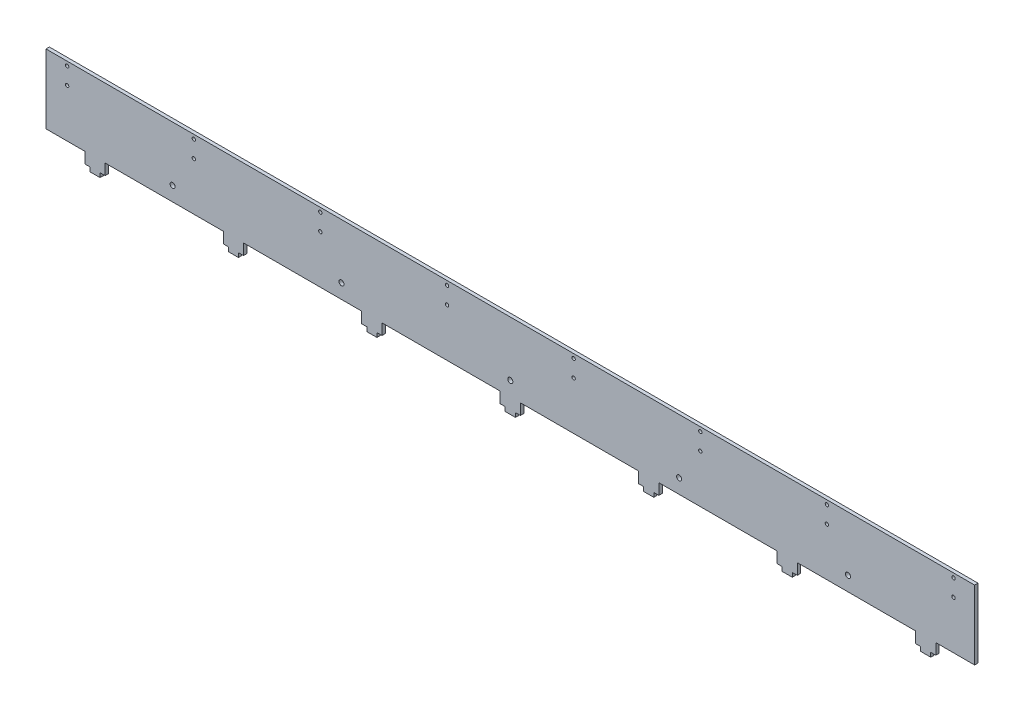
SolidWorks part; units mm, degrees
ref_plane "Спереди" through (0, 0, 0) normal (0, 0, 1) x (1, 0, 0)
ref_plane "Сверху" through (0, 0, 0) normal (0, 1, 0) x (1, 0, 0)
ref_plane "Справа" through (0, 0, 0) normal (1, 0, 0) x (0, 0, -1)
sketch "Эскиз1" plane through (0, 0, 0) normal (0, 0, 1) x (1, 0, 0)
  line L1 (-550, -47.5) -> (550, -47.5)
  line L2 (-550, -47.5) -> (-550, 47.5)
  line L3 (-550, 47.5) -> (550, 47.5)
  line L4 (550, -47.5) -> (550, 47.5)
  line L5 (0, 47.5) -> (0, -47.5) construction
  line L6 (-550, 0) -> (550, 0) construction
  point P0 (0, 0)
  dimension "D1" = 95
  dimension "D2" = 1100
extrude "Бобышка-Вытянуть1" add sketch "Эскиз1" along normal mid plane 4
sketch "Эскиз2" plane through (0, 0, 2) normal (0, 0, 1) x (1, 0, 0)
  line L0 (-550, -47.5) -> (550, -47.5) construction
  line L1 (-550, -47.5) -> (-504, -47.5)
  line L2 (-550, -47.5) -> (-550, -34.5)
  line L3 (-550, -34.5) -> (-504, -34.5)
  line L4 (-504, -47.5) -> (-504, -34.5)
  line L5 (550, -47.5) -> (504, -47.5)
  line L6 (550, -47.5) -> (550, -34.5)
  line L7 (550, -34.5) -> (504, -34.5)
  line L8 (504, -47.5) -> (504, -34.5)
  line L9 (-480, -34.5) -> (-340, -34.5)
  line L10 (-480, -34.5) -> (-480, -47.5)
  line L11 (-480, -47.5) -> (-340, -47.5)
  line L12 (-340, -34.5) -> (-340, -47.5)
  line L14 (-316, -34.5) -> (-176, -34.5)
  line L15 (-316, -34.5) -> (-316, -47.5)
  line L16 (-316, -47.5) -> (-176, -47.5)
  line L17 (-176, -34.5) -> (-176, -47.5)
  line L18 (-152, -34.5) -> (-12, -34.5)
  line L19 (-152, -34.5) -> (-152, -47.5)
  line L20 (-152, -47.5) -> (-12, -47.5)
  line L21 (-12, -34.5) -> (-12, -47.5)
  line L22 (12, -34.5) -> (152, -34.5)
  line L23 (12, -34.5) -> (12, -47.5)
  line L24 (12, -47.5) -> (152, -47.5)
  line L25 (152, -34.5) -> (152, -47.5)
  line L26 (176, -34.5) -> (316, -34.5)
  line L27 (176, -34.5) -> (176, -47.5)
  line L28 (176, -47.5) -> (316, -47.5)
  line L29 (316, -34.5) -> (316, -47.5)
  line L30 (340, -34.5) -> (480, -34.5)
  line L31 (340, -34.5) -> (340, -47.5)
  line L32 (340, -47.5) -> (480, -47.5)
  line L33 (480, -34.5) -> (480, -47.5)
  point P20 (-316, -41)
  point P25 (-152, -41)
  point P26 (152, -41)
  point P39 (340, -41)
  dimension "D1" = 13
  dimension "D5" = 24
  dimension "D6" = 140
  dimension "D7" = 24
  dimension "D2" = 24
  dimension "D3" = 140
  dimension "D4" = 140
  dimension "D8" = 24
  dimension "D9" = 140
  dimension "D10" = 24
  dimension "D11" = 140
  dimension "D12" = 24
  dimension "D13" = 140
  dimension "D14" = 24
extrude "Вырез-Вытянуть1" cut sketch "Эскиз2" against normal through all
sketch "Эскиз3" plane through (0, 0, 2) normal (0, 0, 1) x (1, 0, 0)
  line L0 (550, 47.5) -> (-550, 47.5) construction
  line L1 (-550, 47.5) -> (-550, -34.5) construction
  circle A0 centre (-525, 42.5) radius 2
  circle A1 centre (-525, 22.5) radius 2
  dimension "D1" = 4
  dimension "D2" = 5
  dimension "D3" = 20
  dimension "D4" = 25
extrude "Вырез-Вытянуть2" cut sketch "Эскиз3" against normal through all
pattern_linear "Линейный массив1" count 8 spacing 150 along (1, 0, 0) of "Вырез-Вытянуть2"
sketch "Эскиз4" plane through (0, 0, -2) normal (0, 0, -1) x (-1, 0, 0)
  circle A1 centre (-400, -17.5) radius 3
  circle A2 centre (-400, -17.5) radius 3
  dimension "D1" = 0
extrude "Вырез-Вытянуть3" cut sketch "Эскиз4" against normal through all
pattern_linear "Линейный массив2" count 5 spacing 200 along (-1, 0, 0) of "Вырез-Вытянуть3"
sketch "Эскиз5" plane through (0, -47.5, 0) normal (0, -1, 0) x (1, 0, 0)
  line L0 (492, -2) -> (492, 2) construction
  line L1 (480, 2) -> (504, 2) construction
  line L2 (328, -2) -> (328, 2) construction
  line L3 (316, -2) -> (340, -2) construction
  line L4 (504, 2) -> (480, 2)
  line L5 (480, 2) -> (480, -2)
  line L6 (480, -2) -> (504, -2)
  line L7 (504, -2) -> (504, 2)
  line L8 (498, 2) -> (486, 2)
  line L9 (486, 2) -> (486, -2)
  line L10 (486, -2) -> (498, -2)
  line L11 (498, -2) -> (498, 2)
  line L12 (316, 2) -> (340, 2) construction
  line L13 (164, -2) -> (164, 2) construction
  line L14 (316, -2) -> (340, -2)
  line L15 (340, -2) -> (340, 2)
  line L16 (340, 2) -> (316, 2)
  line L17 (316, 2) -> (316, -2)
  line L18 (322, -2) -> (334, -2)
  line L19 (334, -2) -> (334, 2)
  line L20 (334, 2) -> (322, 2)
  line L21 (322, 2) -> (322, -2)
  line L22 (152, -2) -> (176, -2) construction
  line L23 (152, 2) -> (176, 2) construction
  line L24 (0, -2) -> (0, 2) construction
  line L25 (176, 2) -> (152, 2)
  line L26 (152, 2) -> (152, -2)
  line L27 (152, -2) -> (176, -2)
  line L28 (176, -2) -> (176, 2)
  line L29 (170, 2) -> (158, 2)
  line L30 (158, 2) -> (158, -2)
  line L31 (158, -2) -> (170, -2)
  line L32 (170, -2) -> (170, 2)
  line L33 (-12, -2) -> (12, -2) construction
  line L34 (-12, 2) -> (12, 2) construction
  line L36 (-12, -2) -> (12, -2)
  line L37 (12, -2) -> (12, 2)
  line L38 (12, 2) -> (-12, 2)
  line L39 (-12, 2) -> (-12, -2)
  line L40 (-6, -2) -> (6, -2)
  line L41 (6, -2) -> (6, 2)
  line L42 (6, 2) -> (-6, 2)
  line L43 (-6, 2) -> (-6, -2)
  line L44 (-480, 2) -> (-504, 2) construction
  line L46 (-504, -2) -> (-480, -2) construction
  line L48 (-316, 2) -> (-340, 2) construction
  line L50 (-340, -2) -> (-316, -2) construction
  line L52 (-152, 2) -> (-176, 2) construction
  line L54 (-176, -2) -> (-152, -2) construction
  line L56 (-486, 2) -> (-498, 2)
  line L57 (-498, 2) -> (-498, -2)
  line L58 (-498, -2) -> (-486, -2)
  line L59 (-486, -2) -> (-486, 2)
  line L60 (-322, 2) -> (-334, 2)
  line L61 (-334, 2) -> (-334, -2)
  line L62 (-334, -2) -> (-322, -2)
  line L63 (-322, -2) -> (-322, 2)
  line L64 (-158, 2) -> (-170, 2)
  line L65 (-170, 2) -> (-170, -2)
  line L66 (-170, -2) -> (-158, -2)
  line L67 (-158, -2) -> (-158, 2)
  line L68 (-492, -2) -> (-492, 2) construction
  line L69 (-504, 2) -> (-480, 2) construction
  line L70 (-328, -2) -> (-328, 2) construction
  line L71 (-340, 2) -> (-316, 2) construction
  line L72 (-164, -2) -> (-164, 2) construction
  line L73 (-176, 2) -> (-152, 2) construction
  point P85 (-334, 0)
  dimension "D2" = 12
  dimension "D4" = 12
  dimension "D6" = 12
  dimension "D8" = 12
  dimension "D9" = 12
  dimension "D10" = 12
  dimension "D11" = 12
  dimension "D1" = 0
  dimension "D3" = 0
  dimension "D5" = 0
  dimension "D7" = 0
extrude "Бобышка-Вытянуть2" add sketch "Эскиз5" along normal blind 5
equation "\"D7@Эскиз2\"=\"D5@Эскиз2\""
equation "\"D2@Эскиз2\"=\"D5@Эскиз2\""
equation "\"D3@Эскиз2\"=\"D6@Эскиз2\""
equation "\"D4@Эскиз2\"=\"D6@Эскиз2\""
equation "\"D8@Эскиз2\"=\"D5@Эскиз2\""
equation "\"D9@Эскиз2\"=\"D6@Эскиз2\""
equation "\"D10@Эскиз2\"=\"D5@Эскиз2\""
equation "\"D11@Эскиз2\"=\"D6@Эскиз2\""
equation "\"D12@Эскиз2\"=\"D5@Эскиз2\""
equation "\"D13@Эскиз2\"=\"D6@Эскиз2\""
equation "\"D14@Эскиз2\"=\"D5@Эскиз2\""
